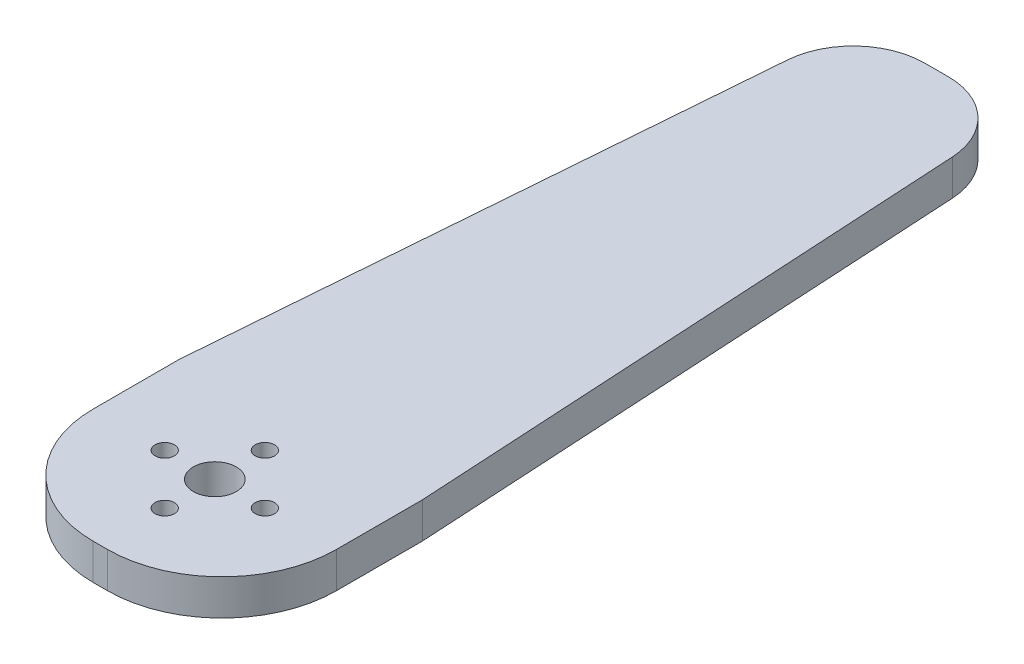
SolidWorks part; units mm, degrees
ref_plane "Front Plane" through (0, 0, 0) normal (0, 0, 1) x (1, 0, 0)
ref_plane "Top Plane" through (0, 0, 0) normal (0, 1, 0) x (1, 0, 0)
ref_plane "Right Plane" through (0, 0, 0) normal (1, 0, 0) x (0, 0, -1)
ref_plane "PY_m5_000" through (0, -5, 0) normal (0, 1, 0) x (1, 0, 0)
sketch "S_prism1" plane through (0, -5, 0) normal (0, 1, 0) x (1, 0, 0)
  line L0 (-1, -16) -> (1, -16)
  line L1 (17, 0) -> (17, 12)
  line L2 (17, 12) -> (12.536, 90.5673)
  line L3 (2.5521, 100) -> (-0.7639, 100)
  line L4 (-10.7324, 90.7929) -> (-17, 12)
  line L5 (-17, 12) -> (-17, 0)
  arc A0 (-17, 0) -> (-1, -16) centre (-1, 0) ccw
  arc A1 (1, -16) -> (17, 0) centre (1, 0) ccw
  arc A2 (12.536, 90.5673) -> (2.5521, 100) centre (2.552, 89.9999) ccw
  arc A3 (-0.7639, 100) -> (-10.7324, 90.7929) centre (-0.7639, 90) ccw
extrude "Boss_1" add sketch "S_prism1" along normal blind 5
ref_plane "PY_m5_100" through (0, -5.1, 0) normal (0, 1, 0) x (1, 0, 0)
sketch "S_hole2" plane through (0, -5.1, 0) normal (0, 1, 0) x (1, 0, 0)
  circle A0 centre (0, 0) radius 3
  dimension "D1_S_hole2" = 6
extrude "Hole_2" cut sketch "S_hole2" along normal blind 5.2
sketch "S_hole3" plane through (0, -5.1, 0) normal (0, 1, 0) x (1, 0, 0)
  circle A0 centre (7, 0) radius 1.35
  dimension "D1_S_hole3" = 2.7
  dimension "P2" = 7
extrude "Hole_3" cut sketch "S_hole3" along normal blind 5.2
sketch "S_hole4" plane through (0, -5.1, 0) normal (0, 1, 0) x (1, 0, 0)
  circle A0 centre (0, -7) radius 1.35
  dimension "D1_S_hole4" = 2.7
  dimension "P2" = 7
extrude "Hole_4" cut sketch "S_hole4" along normal blind 5.2
sketch "S_hole5" plane through (0, -5.1, 0) normal (0, 1, 0) x (1, 0, 0)
  circle A0 centre (-7, 0) radius 1.35
  dimension "D1_S_hole5" = 2.7
  dimension "P2" = 7
extrude "Hole_5" cut sketch "S_hole5" along normal blind 5.2
sketch "S_hole6" plane through (0, -5.1, 0) normal (0, 1, 0) x (1, 0, 0)
  circle A0 centre (0, 7) radius 1.35
  dimension "D1_S_hole6" = 2.7
  dimension "P2" = 7
extrude "Hole_6" cut sketch "S_hole6" along normal blind 5.2
equation "\"plate_t\" = 3"
equation "\"clearance\" = 0.4"
